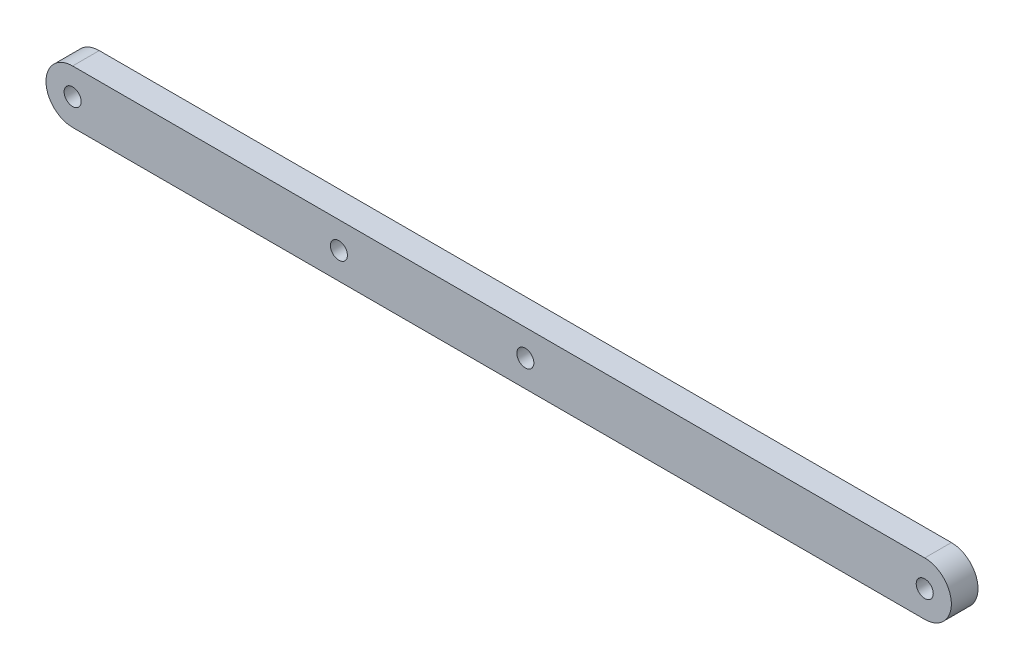
SolidWorks part; units mm, degrees
ref_plane "Front Plane" through (0, 0, 0) normal (0, 0, 1) x (1, 0, 0)
ref_plane "Top Plane" through (0, 0, 0) normal (0, 1, 0) x (1, 0, 0)
ref_plane "Right Plane" through (0, 0, 0) normal (1, 0, 0) x (0, 0, -1)
sketch "Sketch2" plane through (0, 0, 0) normal (0, 0, 1) x (1, 0, 0)
  line L0 (0, 0) -> (203.2, 0) construction
  line L1 (0, 6.35) -> (203.2, 6.35)
  line L2 (0, -6.35) -> (203.2, -6.35)
  arc A0 (0, 6.35) -> (0, -6.35) centre (0, 0) ccw
  arc A1 (203.2, -6.35) -> (203.2, 6.35) centre (203.2, 0) ccw
  circle A2 centre (0, 0) radius 2.032
  circle A3 centre (203.2, 0) radius 2.032
  circle A4 centre (63.5, 0) radius 2.032
  circle A5 centre (107.95, 0) radius 2.032
  point P3 (101.6, 0)
  point P18 (55.8801, 16.0061)
  dimension "D3" = 4.064
  dimension "D4" = 63.5
  dimension "D5" = 4.064
  dimension "D6" = 107.95
  dimension "D1" = 203.2
  dimension "D2" = 12.7
extrude "Boss-Extrude1" add sketch "Sketch2" along normal mid plane 6.35
